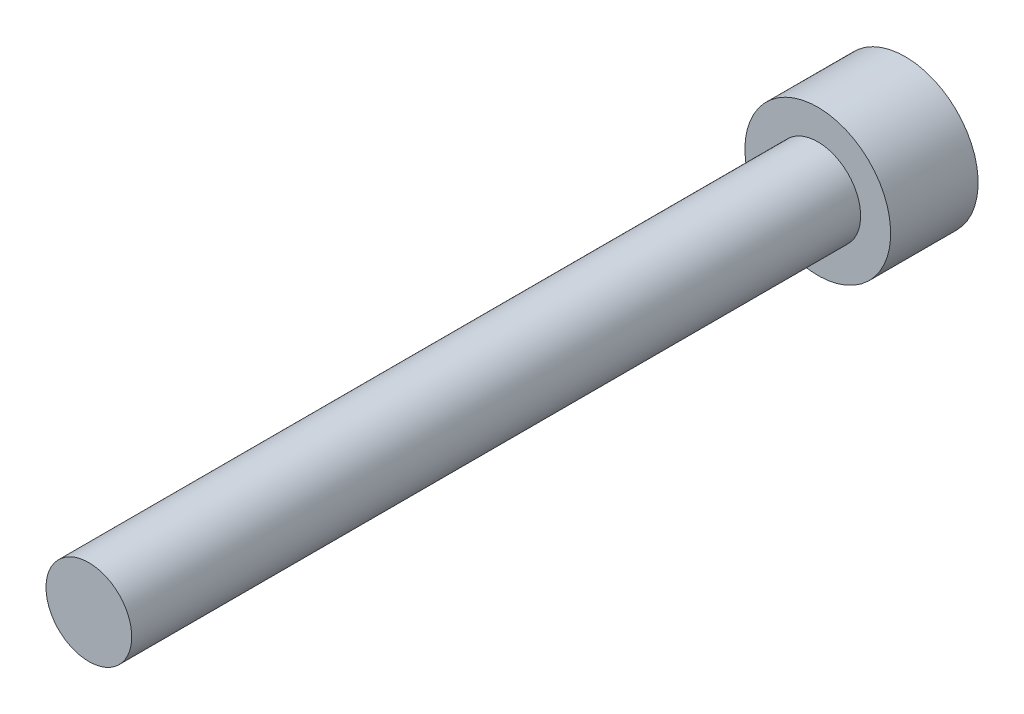
SolidWorks part; units mm, degrees
material "Plain Carbon Steel"
ref_plane "Front Plane" through (0, 0, 0) normal (0, 0, 1) x (1, 0, 0)
ref_plane "Top Plane" through (0, 0, 0) normal (0, 1, 0) x (1, 0, 0)
ref_plane "Right Plane" through (0, 0, 0) normal (1, 0, 0) x (0, 0, -1)
sketch "Sketch1" plane through (0, 0, 0) normal (0, 1, 0) x (1, 0, 0)
  line L0 (0, 33.516) -> (0, 12.152) construction
  line L1 (0, 6) -> (-5, 6)
  line L2 (-5, 6) -> (-5, 0)
  line L3 (-5, 0) -> (-2.94, 0)
  line L4 (-2.94, 0) -> (-2.94, -50)
  line L5 (-2.94, -50) -> (0, -50)
  line L6 (-2.94, 0) -> (0, 0) construction
  line L7 (0, 6) -> (0, -50)
  dimension "D1" = 5.88
  dimension "D2" = 10
  dimension "D3" = 6
  dimension "D4" = 50
revolve "Revolve1" add sketch "Sketch1" angle 360 about L7
cosmetic thread "Cosmetic Thread1" [suppressed] parameters "D2"=4.11
sketch "Sketch2" plane through (0, 0, -6) normal (0, 0, -1) x (-1, 0, 0)
  line L1 (-1.6657, 2.885) -> (-3.3313, 0)
  line L2 (-3.3313, 0) -> (-1.6657, -2.885)
  line L3 (-1.6657, -2.885) -> (1.6657, -2.885)
  line L4 (1.6657, -2.885) -> (3.3313, 0)
  line L5 (3.3313, 0) -> (1.6657, 2.885)
  line L6 (1.6657, 2.885) -> (-1.6657, 2.885)
  circle A0 centre (0, 0) radius 2.885 construction
  dimension "D1" = 5.77
extrude "Cut-Extrude1" cut sketch "Sketch2" against normal blind 2.5
sketch "Sketch3" plane through (0, 0, 0) normal (0, 1, 0) x (1, 0, 0)
  line L0 (-3.3313, 6) -> (-1.3313, 4)
  line L2 (-1.3313, 4) -> (-1.3313, 6)
  line L3 (5, 6) -> (-5, 6) construction
  line L4 (-1.3313, 6) -> (-3.3313, 6)
  line L5 (0, 0) -> (0, 6) construction
  dimension "D1" = 45
  dimension "D2" = 2
revolve "Cut-Revolve1" cut sketch "Sketch3" angle 360 about L5
equation "\"length\" = 50mm"
equation "\"D4@Sketch1\"=\"length\""
